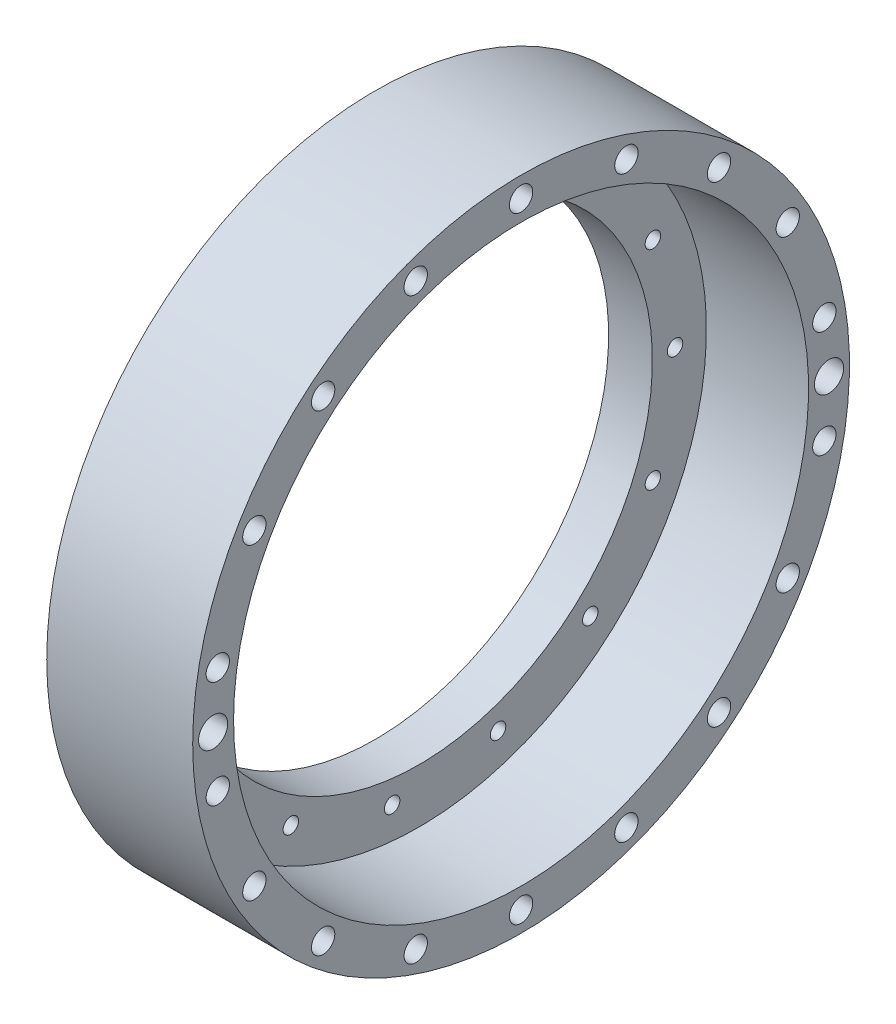
SolidWorks part; units mm, degrees
ref_plane "Front Plane" through (0, 0, 0) normal (0, 0, 1) x (1, 0, 0)
ref_plane "Top Plane" through (0, 0, 0) normal (0, 1, 0) x (1, 0, 0)
ref_plane "Right Plane" through (0, 0, 0) normal (1, 0, 0) x (0, 0, -1)
sketch "Sketch1" plane through (0, 0, 0) normal (0, 0, 1) x (1, 0, 0)
  line L0 (0, 0) -> (146.0265, 0) construction
  line L1 (0, 112.5) -> (0, 80)
  line L2 (0, 80) -> (15, 80)
  line L3 (15, 80) -> (15, 98.5)
  line L4 (15, 98.5) -> (50, 98.5)
  line L5 (50, 98.5) -> (50, 112.5)
  line L6 (50, 112.5) -> (0, 112.5)
  dimension "D1" = 112.5
  dimension "D2" = 80
  dimension "D3" = 15
  dimension "D4" = 50
  dimension "D5" = 98.5
revolve "Revolve1" add sketch "Sketch1" angle 360 about L0
ref_axis "Axis1" through (50, 0, 0) along (-1, 0, 0)
sketch "Sketch3" plane through (50, 0, 0) normal (1, 0, 0) x (0, 0, -1)
  line L0 (0, 0) -> (0, 40.4888) construction
  line L1 (98.5, 0) -> (112.5, 0) construction
  circle A0 centre (0, 0) radius 98.5 construction
  circle A1 centre (0, 0) radius 98.5 construction
  circle A2 centre (0, 0) radius 112.5 construction
  circle A3 centre (105.5, 0) radius 5
  circle A4 centre (-105.5, 0) radius 5
  dimension "D1" = 10
extrude "Cut-Extrude1" cut sketch "Sketch3" against normal through all
sketch "Sketch4" plane through (50, 0, 0) normal (1, 0, 0) x (0, 0, -1)
  line L0 (0, 112.5) -> (0, 98.5) construction
  circle A0 centre (0, 0) radius 112.5 construction
  circle A1 centre (0, 0) radius 98.5 construction
  point P7 (0, 105.5)
hole_wizard "Ø8.0mm Dowel Hole1" positions "3DSketch1" profile "Sketch5" hole size "Ø8.0" standard "ISO" end condition through all
sketch3d "3DSketch1"
  point P0 (50, 105.5, 0)
sketch "Sketch5" plane through (50, 105.5, 0) normal (0, 1, 0) x (0, 0, -1)
  line L0 (0, 0) -> (0, 50)
  line L1 (0, 50) -> (4, 50)
  line L2 (4, 50) -> (4, 0)
  line L5 (4, 0) -> (0, 0)
  line L11 (0, -6.35) -> (0, 107.95) construction
  dimension "Thru Hole Dia." = 8
  dimension "Thru Hole Depth" = 50
pattern_circular "CirPattern1" count 18 over 360 about axis through (50, 0, 0) along (-1, 0, 0) of "Ø8.0mm Dowel Hole1"
sketch "Sketch7" plane through (15, 0, 0) normal (1, 0, 0) x (0, 0, -1)
  circle A0 centre (87.75, 0) radius 2.65
  circle A1 centre (0, 0) radius 87.75 construction
  dimension "D1" = 175.5
  dimension "D2" = 5.3
extrude "Cut-Extrude2" cut sketch "Sketch7" against normal through all
pattern_circular "CirPattern2" count 15 over 360 about axis through (50, 0, 0) along (-1, 0, 0) of "Cut-Extrude2"
